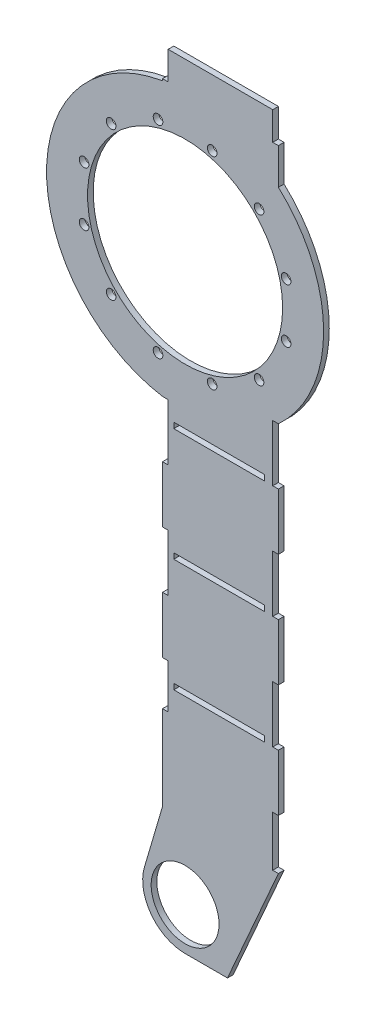
SolidWorks part; units mm, degrees
ref_plane "前视基准面" through (0, 0, 0) normal (0, 0, 1) x (1, 0, 0)
ref_plane "上视基准面" through (0, 0, 0) normal (0, 1, 0) x (1, 0, 0)
ref_plane "右视基准面" through (0, 0, 0) normal (1, 0, 0) x (0, 0, -1)
sketch "草图1" plane through (0, 0, 0) normal (0, 0, 1) x (1, 0, 0)
  line L93 (-8, -48.3425) -> (-6, -48.3425)
  line L100 (-6, -48.3425) -> (-6, -68.3425)
  line L101 (-6, -68.3425) -> (-8, -68.3425)
  line L102 (-8, -68.3425) -> (-8, -88.3425)
  line L103 (-8, -88.3425) -> (-6, -88.3425)
  line L104 (-6, -88.3425) -> (-6, -108.3425)
  line L105 (-6, -108.3425) -> (-8, -108.3425)
  line L106 (-8, -108.3425) -> (-8, -128.3425)
  line L108 (33, -36.2215) -> (31, -36.2215)
  line L109 (31, -36.2215) -> (31, -56.2215)
  line L110 (31, -56.2215) -> (33, -56.2215)
  line L111 (33, -56.2215) -> (33, -76.2215)
  line L112 (33, -76.2215) -> (31, -76.2215)
  line L113 (31, -76.2215) -> (31, -96.2215)
  line L114 (31, -96.2215) -> (33, -96.2215)
  line L117 (33, -96.2215) -> (33, -116.2215)
  line L118 (33, -116.2215) -> (31, -116.2215)
  line L119 (31, -116.2215) -> (31, -136.2215)
  line L120 (31, -136.2215) -> (33, -136.2215)
  line L122 (-8, 49) -> (-8, 48.3425)
  line L125 (33, 49) -> (33, 36.2215)
  line L128 (-4, -56.2215) -> (-4, -54.2215)
  line L129 (-4, -54.2215) -> (28, -54.2215)
  line L130 (28, -54.2215) -> (28, -56.2215)
  line L131 (-4, -56.2215) -> (28, -56.2215)
  line L134 (-4, -94.2215) -> (28, -94.2215)
  line L135 (-4, -96.2215) -> (28, -96.2215)
  line L136 (28, -94.2215) -> (28, -96.2215)
  line L137 (-4, -96.2215) -> (-4, -94.2215)
  line L138 (-4, -134.2215) -> (28, -134.2215)
  line L139 (-4, -136.2215) -> (28, -136.2215)
  line L140 (28, -134.2215) -> (28, -136.2215)
  line L141 (-4, -136.2215) -> (-4, -134.2215)
  line L146 (-8, -174) -> (-14.3926, -195.7746)
  line L148 (0, -215) -> (15, -215)
  line L150 (-6, 59) -> (-6, 49)
  line L151 (15, -215) -> (33, -174)
  line L152 (-6, 49) -> (-8, 49)
  line L153 (33, 49) -> (31, 49)
  line L154 (31, 49) -> (31, 59)
  line L155 (31, 59) -> (-6, 59)
  line L156 (-8, -128.3425) -> (-6, -128.3425)
  line L160 (33, -136.2215) -> (33, -156.2215)
  line L161 (33, -156.2215) -> (31, -156.2215)
  line L162 (31, -156.2215) -> (31, -174)
  line L163 (31, -174) -> (33, -174)
  line L164 (-6, -128.3425) -> (-6, -144)
  line L165 (-6, -144) -> (-8, -144)
  line L167 (-8, -144) -> (-8, -174)
  circle A13 centre (0, 0) radius 34.5
  arc A55 (-8, -48.3425) -> (-8, 48.3425) centre (0, 0) cw
  arc A56 (33, -36.2215) -> (33, 36.2215) centre (0, 0) ccw
  arc A61 (-14.3926, -195.7746) -> (0, -215) centre (0, -200) ccw
  circle A62 centre (0, -200) radius 12
  circle A64 centre (26.163, 26.163) radius 1.7
  circle A65 centre (35.7393, 9.5763) radius 1.7
  circle A66 centre (9.5763, 35.7393) radius 1.7
  circle A67 centre (-9.5763, 35.7393) radius 1.7
  circle A68 centre (-26.163, 26.163) radius 1.7
  circle A69 centre (-35.7393, 9.5763) radius 1.7
  circle A70 centre (-35.7393, -9.5763) radius 1.7
  circle A71 centre (-26.163, -26.163) radius 1.7
  circle A72 centre (-9.5763, -35.7393) radius 1.7
  circle A73 centre (9.5763, -35.7393) radius 1.7
  circle A74 centre (26.163, -26.163) radius 1.7
  circle A75 centre (35.7393, -9.5763) radius 1.7
  dimension "D1" = 3
extrude "凸台-拉伸1" add sketch "草图1" along normal blind 2 contours A13 region at (7.804, -69.8034, 0)
